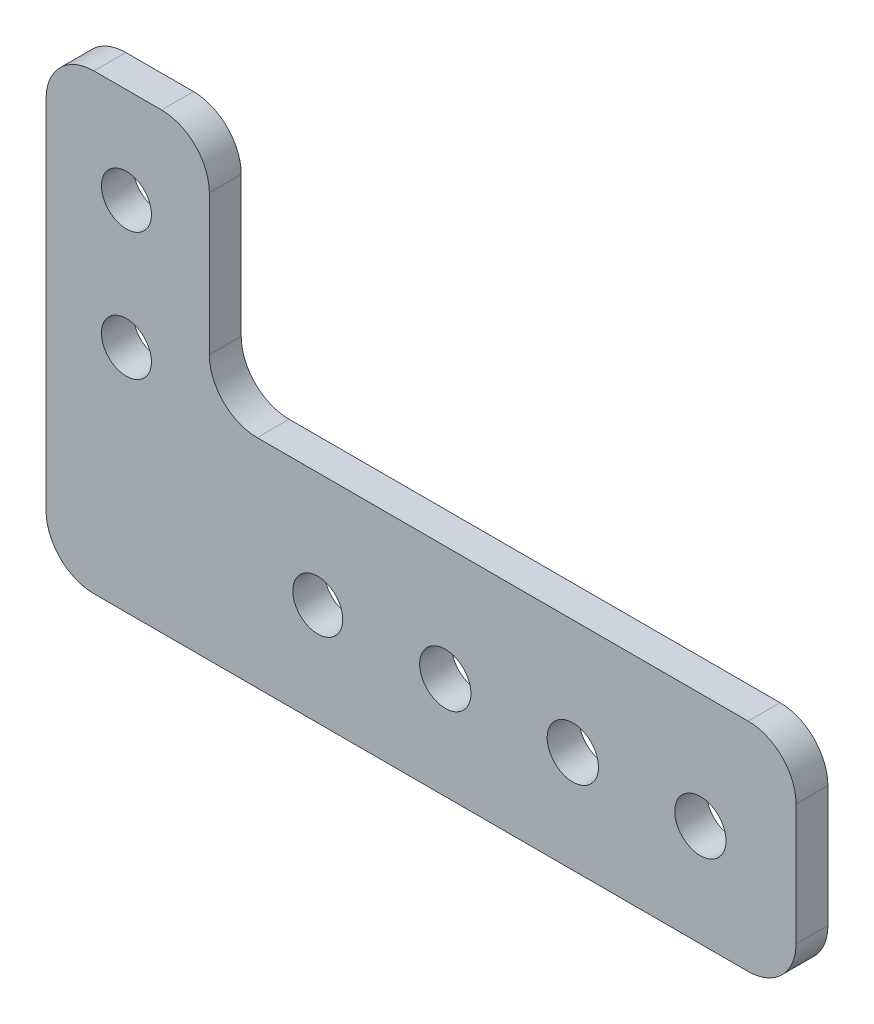
SolidWorks part; units mm, degrees
material "6061-T6 (SS)"
ref_plane "Front Plane" through (0, 0, 0) normal (0, 0, 1) x (1, 0, 0)
ref_plane "Top Plane" through (0, 0, 0) normal (0, 1, 0) x (1, 0, 0)
ref_plane "Right Plane" through (0, 0, 0) normal (1, 0, 0) x (0, 0, -1)
sketch "Sketch1" plane through (0, 0, 0) normal (0, 0, 1) x (1, 0, 0)
  line L0 (-17.145, 23.8125) -> (-33.401, 23.8125) construction
  line L1 (-41.275, -23.8125) -> (41.275, -23.8125)
  line L2 (-41.275, -23.8125) -> (-41.275, 23.8125)
  line L3 (-41.275, 23.8125) -> (41.275, 23.8125)
  line L4 (41.275, -23.8125) -> (41.275, 23.8125)
  line L5 (-41.275, -23.8125) -> (41.275, 23.8125) construction
  line L6 (-41.275, 23.8125) -> (41.275, -23.8125) construction
  line L7 (41.275, 23.8125) -> (-17.145, 23.8125)
  line L8 (41.275, 23.8125) -> (41.275, 0.3175)
  line L9 (41.275, 0.3175) -> (-17.145, 0.3175)
  line L10 (-17.145, 23.8125) -> (-17.145, 0.3175)
  line L11 (-41.275, -23.8125) -> (-33.401, -23.8125)
  line L12 (-41.275, -23.8125) -> (-41.275, 23.8125)
  line L13 (-41.275, 23.8125) -> (-33.401, 23.8125)
  line L14 (-33.401, -23.8125) -> (-33.401, 23.8125)
  line L15 (-33.401, -23.8125) -> (41.275, -23.8125)
  line L16 (-33.401, -23.8125) -> (-33.401, -21.2725)
  line L17 (-33.401, -21.2725) -> (41.275, -21.2725)
  line L18 (41.275, -23.8125) -> (41.275, -21.2725)
  circle A0 centre (-25.4, -11.1125) radius 2.4892
  circle A1 centre (-25.4, 1.5875) radius 2.4892
  circle A2 centre (-25.4, 14.2875) radius 2.4892
  circle A4 centre (-6.35, -11.1125) radius 2.4892
  circle A5 centre (6.35, -11.1125) radius 2.5527
  circle A6 centre (19.05, -11.1125) radius 2.5527
  circle A7 centre (31.75, -11.1125) radius 2.5527
  point P0 (0, 0)
  point P31 (0, 0)
  point P32 (0, 0)
  dimension "D7" = 19.05
  dimension "D17" = 12.7
  dimension "D18" = 5.1054
  dimension "D19" = 4.9784
  dimension "D1" = 82.55
  dimension "D2" = 9.525
  dimension "D3" = 24.13
  dimension "D4" = 24.13
  dimension "D5" = 7.874
  dimension "D6" = 47.625
  dimension "D8" = 15.875
  dimension "D9" = 12.7
  dimension "D10" = 12.7
  dimension "D11" = 12.7
  dimension "D12" = 8.001
  dimension "D13" = 12.7
  dimension "D14" = 27.051
  dimension "D15" = 12.7
  dimension "D16" = 2.54
extrude "Boss-Extrude1" add sketch "Sketch1" along normal blind 3.175 contours L14 L17 L4 L9 L10 L3 A6 A5 A4 A2 A1 A0 | A0 region at (-1.5463, -6.188, 0) region at (-25.4, -11.1125, 0)
fillet "Fillet1" radius 4.7625 6 edges at (-33.401, 23.8125, 1.5875) (-17.145, 23.8125, 1.5875) (-17.145, 0.3175, 1.5875) (41.275, 0.3175, 1.5875) (41.275, -21.2725, 1.5875) (-33.401, -21.2725, 1.5875)
